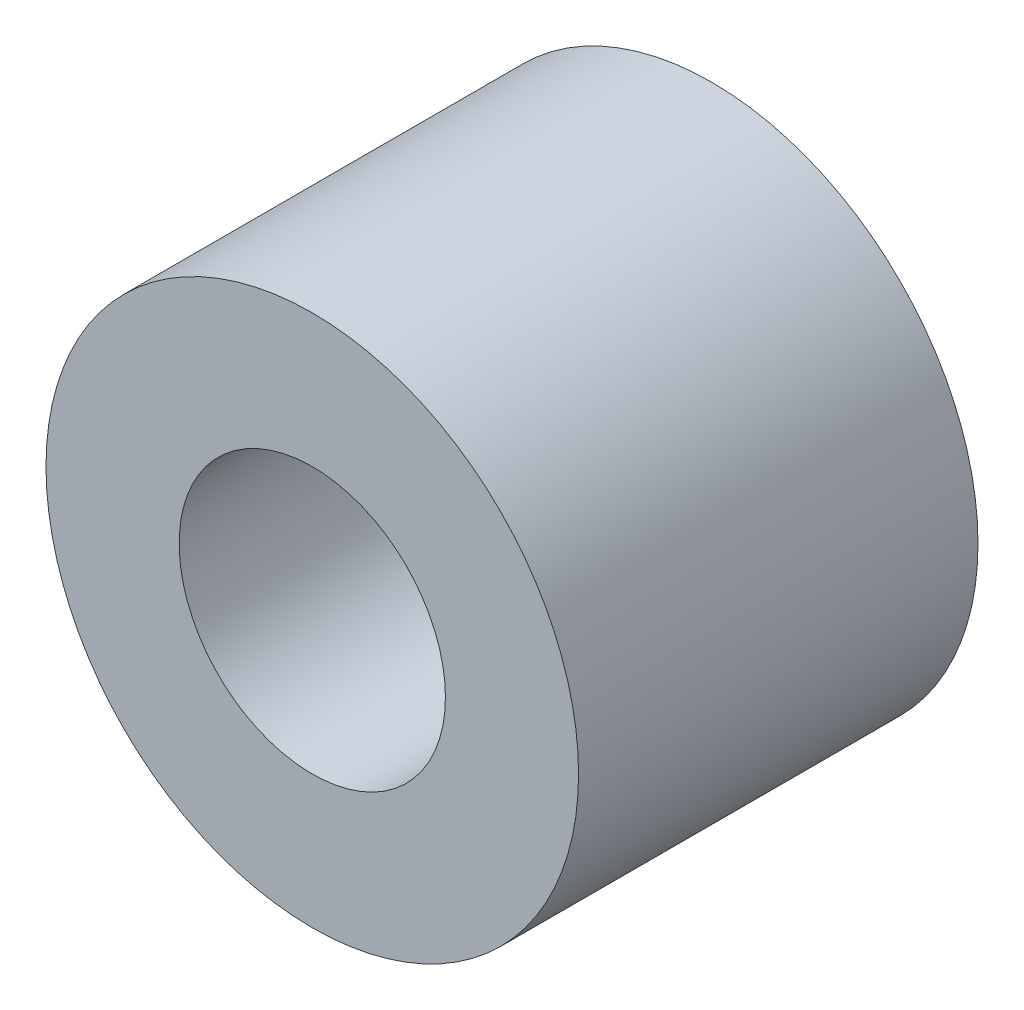
SolidWorks part; units mm, degrees
ref_plane "Plano frontal" through (0, 0, 0) normal (0, 0, 1) x (1, 0, 0)
ref_plane "Plano superior" through (0, 0, 0) normal (0, 1, 0) x (1, 0, 0)
ref_plane "Plano direito" through (0, 0, 0) normal (1, 0, 0) x (0, 0, -1)
sketch "Esboço1" plane through (0, 0, 0) normal (0, 0, 1) x (1, 0, 0)
  arc A3 (-24.3819, -51.2653) -> (-2.4708, -20.6405) centre (-58.901, -3.4172) ccw
  arc A4 (-17.0686, -61.4026) -> (9.4286, 17.6381) centre (-58.901, -3.4172) ccw
  arc A5 (-33.5653, -42.409) -> (-15.335, 12.8389) centre (-58.901, -3.4172) ccw
  arc A6 (-24.3819, -51.2653) -> (19.9977, -73.6125) centre (-8, -73.9728) ccw
  arc A7 (-17.0686, -61.4026) -> (-23.5, -73.9728) centre (-8, -73.9728) ccw
  arc A11 (23, -58.9728) -> (19.9977, -73.6125) centre (54.9948, -73.162) ccw
  arc A22 (19.1336, -56.7257) -> (16.8471, -61.1871) centre (53.0718, -76.936) ccw
  arc A23 (27.1732, -60.7116) -> (24.9949, -73.6125) centre (55.4585, -72.1219) ccw
  circle A24 centre (0, 0) radius 10
  circle A25 centre (0, 0) radius 20
  arc A26 (8.4454, -85.3538) -> (13.4536, -73.6247) centre (-9.3737, -70.8115) ccw
  arc A27 (-23.5, -73.9728) -> (8.4454, -85.3538) centre (-5.5, -73.9728) ccw
  arc A28 (16.8471, -61.1871) -> (13.4536, -73.6247) centre (58.1157, -79.1288) ccw
  arc A30 (-51.2801, -83.9656) -> (-4, -113.5114) centre (-13.9544, -76.8384) ccw
  arc A32 (-33.5653, -42.409) -> (-51.2801, -83.9656) centre (-11.4988, -76.3695) ccw
  arc A34 (-4, -113.5114) -> (24.9949, -73.6125) centre (-14.3081, -75.5355) ccw
  point P3 (-2.4708, -20.6405)
  point P27 (0, 0)
  point P28 (53.5197, -96.5845)
  point P29 (-11.3743, -86.9078)
  point P30 (51.292, -92.3431)
  point P33 (22.1823, -81.2624)
  point P34 (51.9995, -85.4902)
  point P36 (0, 0)
  point P37 (23.8256, -75.1857)
  point P39 (19.9977, -82.1807)
  point P42 (23.1724, -80.7302)
  point P43 (0, 0)
  point P44 (25.581, -71.773)
  point P45 (27.1998, -60.6442)
  point P46 (19.9977, -82.0781)
  point P47 (0, 0)
  point P48 (-5.5, -118.8733)
  point P49 (-9.8661, -121.3815)
  point P50 (-9.8661, -120.1661)
  point P51 (-9.0181, -119.9944)
  point P52 (0, 0)
  point P53 (-6.4774, -119.2882)
  point P54 (23.5317, -79.8269)
  point P55 (-4, -119.2585)
  point P56 (19.9977, -82.0041)
  point P57 (23, -64.3655)
  point P58 (0, 0)
  point P59 (19.9977, -78.984)
  point P60 (19.9977, -79.5654)
  point P61 (24.9977, -68.7796)
  point P62 (0, 0)
  point P63 (0, 0)
  point P64 (0, 0)
  point P65 (0, 0)
  point P66 (17.4791, -58.8779)
  point P67 (0, 0)
  point P68 (0, 0)
  point P69 (0, 0)
  point P70 (27.7747, -58.7764)
  point P71 (0, 0)
  point P72 (0, 0)
  point P73 (0, 0)
  point P74 (13.4703, -73.491)
  point P75 (0, 0)
  point P76 (0, 0)
  point P77 (0, 0)
  dimension "D1" = 118
  dimension "D2" = 93
  dimension "D3" = 143
  dimension "D4" = 56
  dimension "D5" = 70
  dimension "D6" = 20
  dimension "D7" = 40
  dimension "D9" = 46
  dimension "D10" = 79
  dimension "D11" = 4
  dimension "D12" = 61
  dimension "D15" = 15
  dimension "D17" = 36
  dimension "D18" = 90
  dimension "D19" = 76
  dimension "D16" = 81
  dimension "D13" = 8
  dimension "D14" = 31
extrude "Ressalto-extrusão1" add sketch "Esboço1" along normal blind 15 and the other way blind 15 contours A4 A25 A5 A24 | A4 A25 | A5 A25 region at (-1.4723, -19.4565, 0) region at (15.1196, 0.8772, 0) region at (-15.9213, -0.9237, 0)
ref_plane "Plano1" through (-24.3819, -51.2653, 0) normal (0.811, 0.5851, 0) x (0, 0, -1)
sketch "Esboço2" plane through (-24.3819, -51.2653, 0) normal (0.811, 0.5851, 0) x (0, 0, -1)
  ellipse E0 centre (0, 0) end of major axis (0, -12.5) minor radius 10
  point P1 (0, 0)
  dimension "D1" = 25
  dimension "D2" = 20
sketch3d "3DSketch5"
  circle A0 centre (-4, -101.6856, 0) radius 10
  arc A1 (-24.3819, -51.2653, 0) -> (19.9977, -73.6125, 0) centre (-8, -73.9728, 0) ccw construction
  point P4 (6, -101.6856, 0)
  point P8 (-8, -73.9728, 28)
  dimension "D2" = 20
  dimension "D1" = 4
sketch3d "3DSketch6"
  arc A0 (-24.3819, -51.2653, 0) -> (19.9977, -73.6125, 0) centre (-8, -73.9728, 0) ccw construction
  circle A1 centre (19.9977, -73.6125, 0) radius 5
  point P5 (-8, -73.9728, 28)
  point P9 (20.062, -78.6121, 0)
  dimension "D1" = 10
